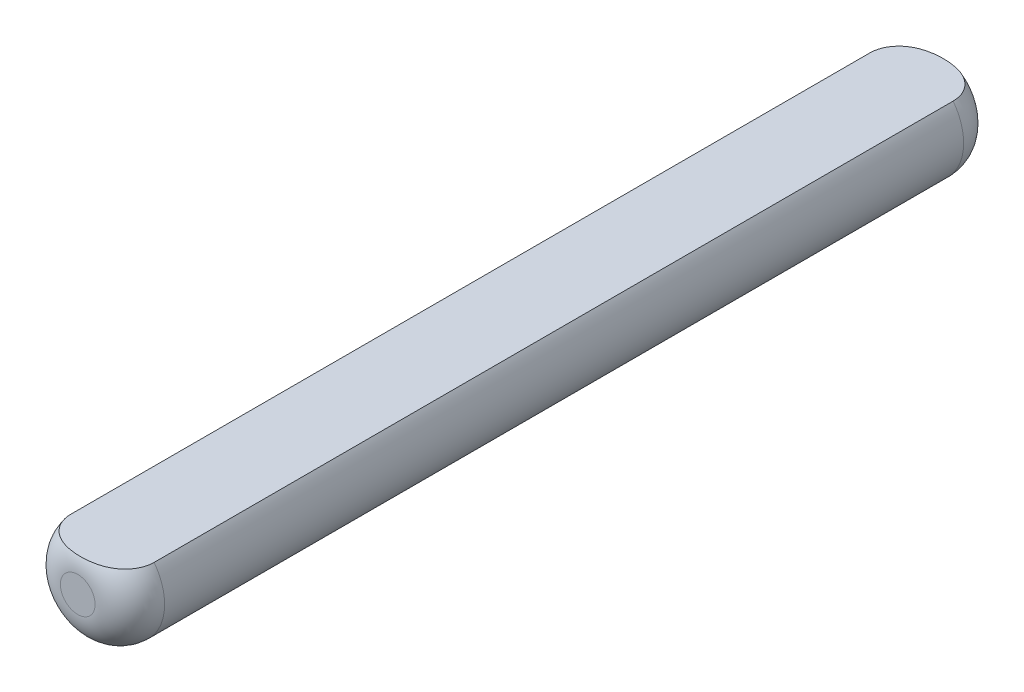
SolidWorks part; units mm, degrees
ref_plane "Plan de face" through (0, 0, 0) normal (0, 0, 1) x (1, 0, 0)
ref_plane "Plan de dessus" through (0, 0, 0) normal (0, 1, 0) x (1, 0, 0)
ref_plane "Plan de droite" through (0, 0, 0) normal (1, 0, 0) x (0, 0, -1)
sketch "Esquisse1" plane through (0, 0, 0) normal (0, 0, 1) x (1, 0, 0)
  circle A0 centre (0, 0) radius 3
  dimension "D1" = 6
extrude "Boss.-Extru.1" add sketch "Esquisse1" along normal blind 50
fillet "Congé1" radius 2 2 edges at (3, 0, 0) (3, 0, 50)
sketch "Esquisse2" plane through (0, 0, 50) normal (0, 0, 1) x (1, 0, 0)
  line L1 (-3, 3) -> (3, 3)
  line L2 (-3, 3) -> (-3, 1.8)
  line L3 (-3, 1.8) -> (3, 1.8)
  line L4 (3, 3) -> (3, 1.8)
  circle A0 centre (0, 0) radius 3 construction
  point P6 (0, 3)
  dimension "D1" = 6
  dimension "D2" = 1.2
extrude "Enlèv. mat.-Extru.1" cut sketch "Esquisse2" against normal through all
sketch "Esquisse3" plane through (0, 0, 0) normal (0, 0, -1) x (-1, 0, 0)
  point P0 (0, 0)
